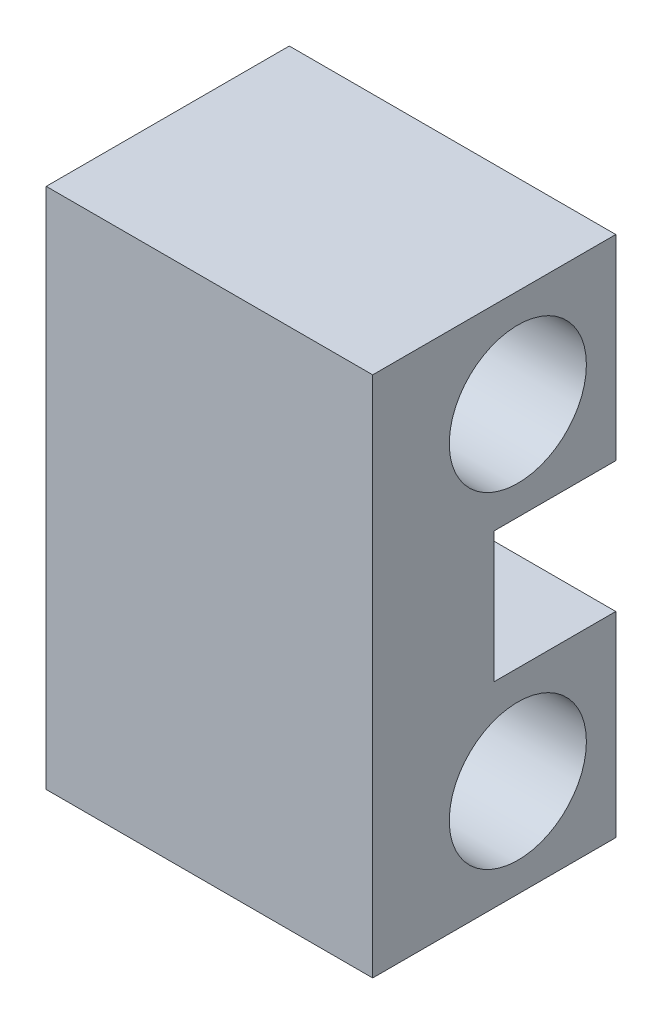
SolidWorks part; units mm, degrees
ref_plane "Спереди" through (0, 0, 0) normal (0, 0, 1) x (1, 0, 0)
ref_plane "Сверху" through (0, 0, 0) normal (0, 1, 0) x (1, 0, 0)
ref_plane "Справа" through (0, 0, 0) normal (1, 0, 0) x (0, 0, -1)
sketch "Эскиз1" plane through (0, 0, 0) normal (1, 0, 0) x (0, 0, -1)
  line L0 (0, 0) -> (0, 80)
  line L1 (0, 80) -> (37.2284, 80)
  line L2 (37.2284, 80) -> (37.2284, 50)
  line L3 (37.2284, 50) -> (18.6142, 50)
  line L4 (18.6142, 50) -> (18.6142, 30)
  line L5 (18.6142, 30) -> (37.2284, 30)
  line L6 (37.2284, 30) -> (37.2284, 0)
  line L7 (37.2284, 0) -> (0, 0)
  line L8 (22.2284, 65) -> (22.2284, 15) construction
  circle A0 centre (22.2284, 15) radius 10.5
  circle A1 centre (22.2284, 65) radius 10.5
  point P13 (26.1802, 8.6053)
  point P15 (0, 0)
  point P16 (0, 0)
  point P17 (27.749, 95.1506)
  point P18 (27.4876, 93.5819)
  dimension "D4" = 21
  dimension "D6" = 21
  dimension "D1" = 30
  dimension "D2" = 15
  dimension "D3" = 15
  dimension "D5" = 15
  dimension "D7" = 15
  dimension "D8" = 50
extrude "Бобышка-Вытянуть2" add sketch "Эскиз1" along normal blind 50
